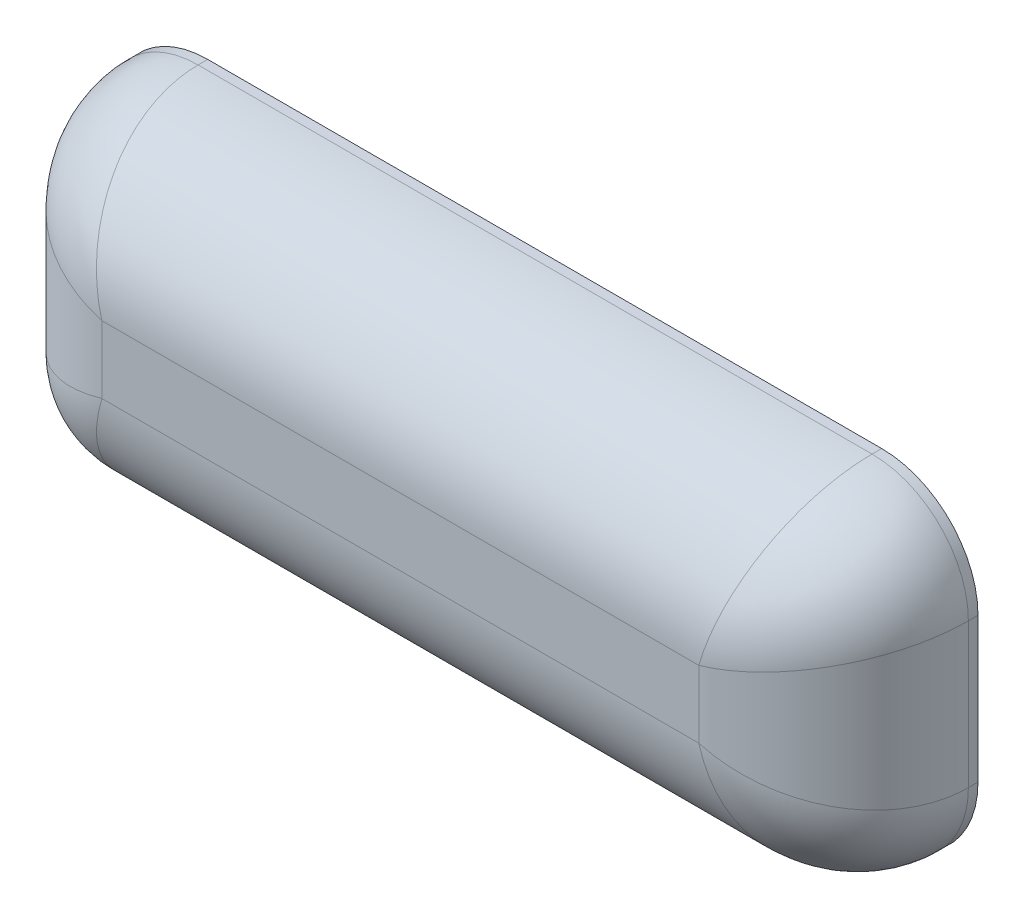
SolidWorks part; units mm, degrees
ref_plane "Front Plane" through (0, 0, 0) normal (0, 0, 1) x (1, 0, 0)
ref_plane "Top Plane" through (0, 0, 0) normal (0, 1, 0) x (1, 0, 0)
ref_plane "Right Plane" through (0, 0, 0) normal (1, 0, 0) x (0, 0, -1)
sketch "Sketch1" plane through (0, 0, 0) normal (0, 0, 1) x (1, 0, 0)
  line L1 (-9, 3.5) -> (9, 3.5)
  line L2 (-9, 3.5) -> (-9, -3.5)
  line L3 (-9, -3.5) -> (9, -3.5)
  line L4 (9, 3.5) -> (9, -3.5)
  line L5 (-9, 3.5) -> (9, -3.5) construction
  line L6 (-9, -3.5) -> (9, 3.5) construction
  point P0 (0, 0)
  dimension "D1" = 7
  dimension "D2" = 18
extrude "Boss-Extrude1" add sketch "Sketch1" along normal blind 3
fillet "Fillet1" radius 2 4 edges at (-9, -3.5, 1.5) (9, -3.5, 1.5) (9, 3.5, 1.5) (-9, 3.5, 1.5)
fillet "Fillet2" radius 2.8 8 edges at (-8.4142, -2.9142, 3) (-9, 0, 3) (-8.4142, 2.9142, 3) (0, 3.5, 3) (8.4142, 2.9142, 3) (9, 0, 3) (8.4142, -2.9142, 3) (0, -3.5, 3)
